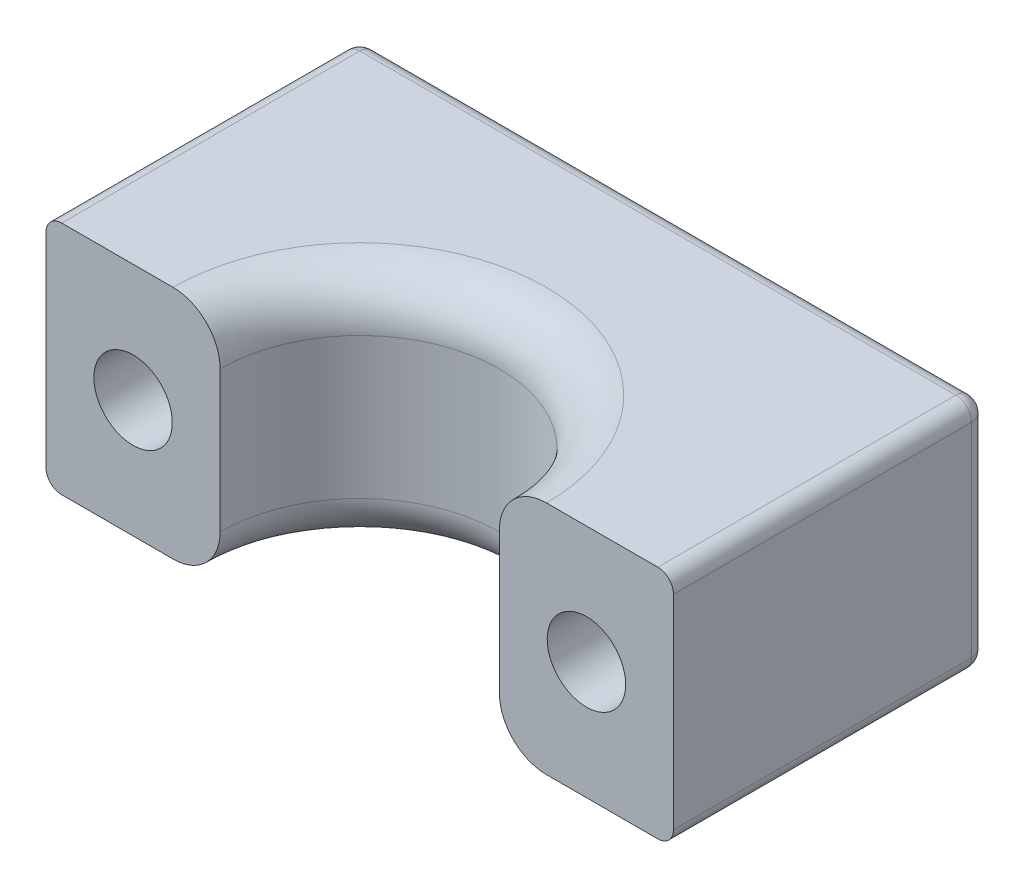
SolidWorks part; units mm, degrees
ref_plane "前基準面" through (0, 0, 0) normal (0, 0, 1) x (1, 0, 0)
ref_plane "上基準面" through (0, 0, 0) normal (0, 1, 0) x (1, 0, 0)
ref_plane "右基準面" through (0, 0, 0) normal (1, 0, 0) x (0, 0, -1)
sketch "草圖1" plane through (0, 0, 0) normal (0, 1, 0) x (1, 0, 0)
  line L1 (0, 0) -> (40, 0)
  line L2 (0, 0) -> (0, 40)
  line L3 (0, 40) -> (40, 40)
  line L4 (40, 0) -> (40, 40)
  dimension "D1" = 40
  dimension "D2" = 40
extrude "填料-伸長1" add sketch "草圖1" along normal blind 15
sketch "草圖3" plane through (0, 15, 0) normal (0, 1, 0) x (1, 0, 0)
  line L0 (0, 20) -> (45.2518, 20) construction
  line L1 (0, 40) -> (0, 0) construction
  line L2 (20, 40) -> (20, -1.2692) construction
  line L3 (40, 40) -> (0, 40) construction
  circle A0 centre (20, 20) radius 8.9
  dimension "D1" = 17.8
extrude "除料-伸長1" cut sketch "草圖3" against normal through all
sketch "草圖5" plane through (0, 0, 0) normal (0, 0, 1) x (1, 0, 0)
  line L0 (40, 7.5) -> (34.45, 7.5) construction
  line L1 (40, 15) -> (40, 0) construction
  line L2 (20, 0) -> (20, 21.8391) construction
  line L3 (0, 0) -> (40, 0) construction
  circle A0 centre (34.45, 7.5) radius 2.5
  circle A1 centre (5.55, 7.5) radius 2.5
  dimension "D2" = 5
  dimension "D1" = 5.55
extrude "除料-伸長2" cut sketch "草圖5" against normal through all
sketch "草圖6" plane through (0, 15, 0) normal (0, 1, 0) x (1, 0, 0)
  line L0 (40, 0) -> (40, 40) construction
  line L1 (0, 0) -> (40, 0)
  line L2 (0, 0) -> (0, 20)
  line L3 (0, 20) -> (40, 20)
  line L4 (40, 0) -> (40, 20)
extrude "除料-伸長3" cut sketch "草圖6" against normal through all
fillet "圓角1" radius 3 2 edges at (20, 0, -28.9) (20, 15, -28.9)
fillet "圓角2" radius 1 3 edges at (0, 15, -30) (40, 15, -30) (20, 15, -40)
fillet "圓角3" radius 1 4 edges at (39.7071, 14.7071, -39.7071) (0.2929, 14.7071, -39.7071) (40, 7, -40) (0, 7, -40)
fillet "圓角4" radius 1 5 edges at (0, 0, -29.5) (0.2929, 0, -39.7071) (20, 0, -40) (39.7071, 0, -39.7071) (40, 0, -29.5)
